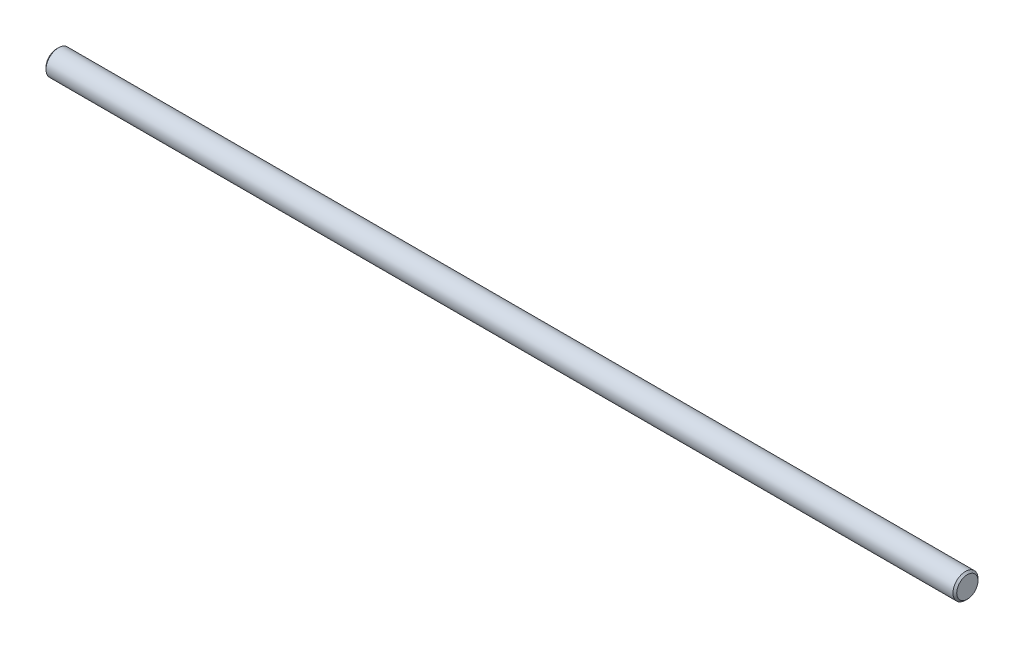
SolidWorks part; units mm, degrees
ref_plane "Front Plane" through (0, 0, 0) normal (0, 0, 1) x (1, 0, 0)
ref_plane "Top Plane" through (0, 0, 0) normal (0, 1, 0) x (1, 0, 0)
ref_plane "Right Plane" through (0, 0, 0) normal (1, 0, 0) x (0, 0, -1)
sketch "Sketch1" plane through (0, 0, 0) normal (0, 0, 1) x (1, 0, 0)
  line L0 (-144.4625, 0) -> (144.4625, 0) construction
  line L1 (144.4625, 3.9688) -> (144.4625, -3.9688) construction
  line L2 (-144.4625, 3.9688) -> (-144.4625, -3.9688) construction
  point P6 (141.6844, -3.9688)
  dimension "Thread Diameter" = 7.9375
  dimension "Length" = 288.925
  dimension "D1" = 2.7781
sketch "Sketch2" plane through (0, 0, 0) normal (1, 0, 0) x (0, 0, -1)
  circle A0 centre (0, 0) radius 3.9688
extrude "Boss-Extrude1" add sketch "Sketch2" against normal up to vertex (144.4625 mm away) and the other way up to vertex (144.4625 mm away) up to point (-144.4625, 0, 0) other way up to point (144.4625, 0, 0)
cosmetic thread "Cosmetic Thread1" parameters "D2"=3.8811
sketch "Sketch3" plane through (144.4625, 0, 0) normal (1, 0, 0) x (0, 0, -1)
  circle A1 centre (0, 0) radius 3.9688
  circle A2 centre (0, 0) radius 3.9688
  dimension "D1" = 0
curve "Helix/Spiral1" pitch 0.7937 height 289.7187 turns 365 parameters "Pitch"=0.7937
chamfer "Chamfer1" distance 0.5953 angle 45 2 edges at (-144.4625, 0, -3.9688) (144.4625, 0, -3.9688)
sketch "Sketch4" plane through (0, 0, 0) normal (0, 0, 1) x (1, 0, 0)
  line L0 (144.4129, 4.0547) -> (144.8098, 3.3673) construction
  line L1 (144.8098, 3.3673) -> (145.2066, 4.0547) construction
  line L2 (145.2066, 4.0547) -> (144.4129, 4.0547) construction
  line L3 (144.8098, 4.0547) -> (144.8098, 3.9688) construction
  line L4 (144.8098, 3.3673) -> (144.8098, 3.4532) construction
  line L5 (144.7602, 3.4532) -> (144.8594, 3.4532) construction
  line L6 (144.4625, 3.9688) -> (145.157, 3.9688) construction
  line L7 (144.7602, 3.4532) -> (144.4377, 4.0117)
  line L8 (144.7602, 3.4532) -> (144.8594, 3.4532)
  line L9 (144.4377, 4.0117) -> (145.1818, 4.0117)
  line L10 (145.1818, 4.0117) -> (144.8594, 3.4532)
  point P13 (144.8098, 4.0117)
  dimension "D2" = 0.0992
sweep "Cut-Sweep3" [suppressed] cut profiles "Sketch4" path "Helix/Spiral1"
equation "\"D3@Helix/Spiral1\" = \"Length@Sketch1\"+\"Pitch@Helix/Spiral1\""
equation "\"D1@Chamfer1\" = \"Pitch@Helix/Spiral1\"*.75"
equation "\"D1@Sketch4\" = \"Pitch@Helix/Spiral1\""
equation "\"D2@Sketch4\" = \"D1@Sketch4\"/8"
equation "\"D1@Sketch1\" = \"Pitch@Helix/Spiral1\"*3.50"
